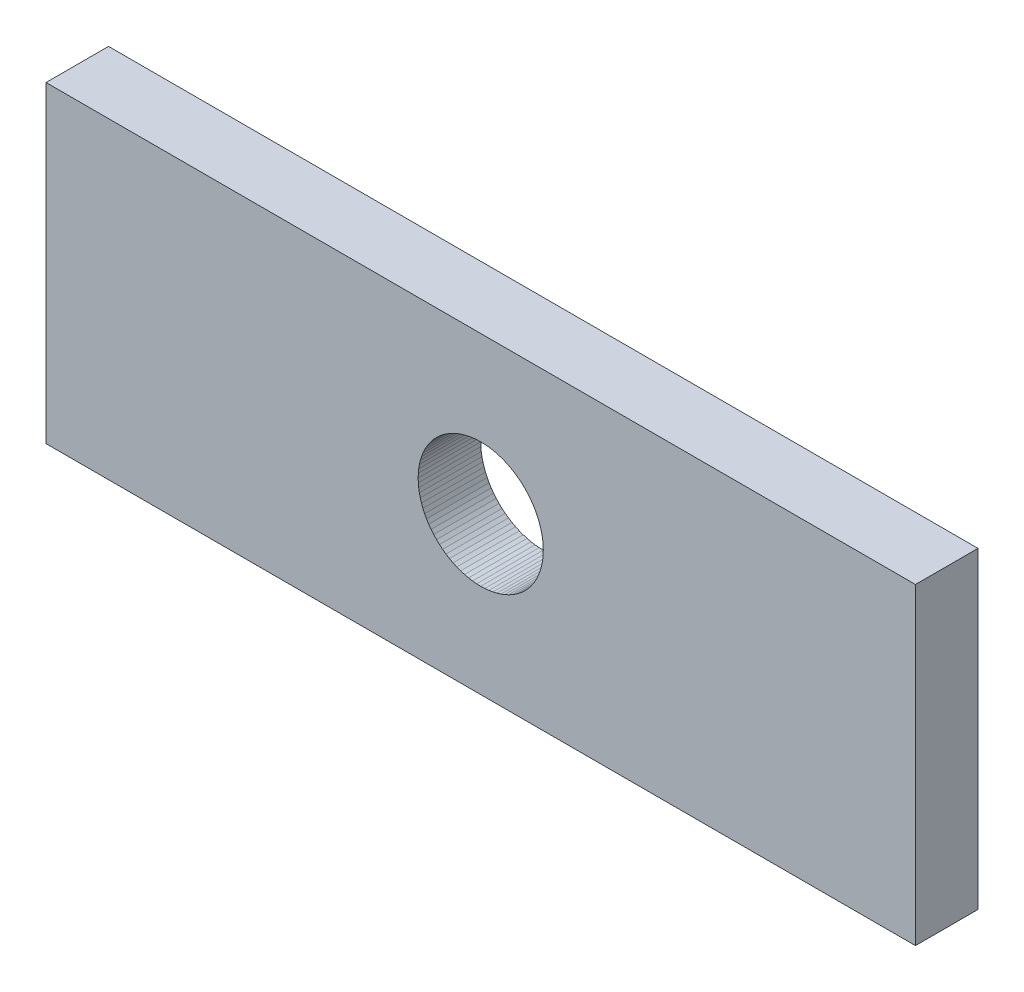
SolidWorks part; units mm, degrees
material "Plain Carbon Steel"
ref_plane "Front Plane" through (0, 0, 0) normal (0, 0, 1) x (1, 0, 0)
ref_plane "Top Plane" through (0, 0, 0) normal (0, 1, 0) x (1, 0, 0)
ref_plane "Right Plane" through (0, 0, 0) normal (1, 0, 0) x (0, 0, -1)
sketch "Model" plane through (0, 0, 0) normal (0, 0, 1) x (1, 0, 0)
  line L0 (1403.0457, -188.9412) -> (1403.0457, -213.9412)
  line L1 (1373.1253, -200.1471) -> (1373.0303, -199.834)
  line L2 (1373.2957, -201.4412) -> (1373.285, -201.1142)
  line L3 (1373.285, -201.7682) -> (1373.2957, -201.4412)
  line L4 (1372.2624, -204.485) -> (1372.453, -204.219)
  line L5 (1372.9151, -199.5278) -> (1372.78, -199.2297)
  line L6 (1371.0735, -205.5985) -> (1371.3395, -205.4079)
  line L7 (1372.9151, -203.3546) -> (1373.0303, -203.0484)
  line L8 (1372.78, -203.6526) -> (1372.9151, -203.3546)
  line L9 (1373.0303, -199.834) -> (1372.9151, -199.5278)
  line L10 (1372.6258, -203.9412) -> (1372.78, -203.6526)
  line L11 (1370.5071, -205.9255) -> (1370.7957, -205.7713)
  line L12 (1372.453, -204.219) -> (1372.6258, -203.9412)
  line L13 (1370.2091, -206.0606) -> (1370.5071, -205.9255)
  line L14 (1373.2529, -200.7885) -> (1373.1996, -200.4657)
  line L15 (1369.5898, -206.2708) -> (1369.9029, -206.1758)
  line L16 (1371.5924, -205.2004) -> (1371.8312, -204.9767)
  line L17 (1370.7957, -205.7713) -> (1371.0735, -205.5985)
  line L18 (1369.2711, -206.3451) -> (1369.5898, -206.2708)
  line L19 (1372.0549, -204.7379) -> (1372.2624, -204.485)
  line L20 (1373.285, -201.1142) -> (1373.2529, -200.7885)
  line L21 (1373.1996, -200.4657) -> (1373.1253, -200.1471)
  line L22 (1363.3064, -201.1142) -> (1363.2957, -201.4412)
  line L23 (1365.7957, -205.7713) -> (1366.0842, -205.9255)
  line L24 (1367.3202, -206.3451) -> (1367.643, -206.3984)
  line L25 (1363.3064, -201.7682) -> (1363.3384, -202.0938)
  line L26 (1333.5457, -188.9412) -> (1403.0457, -188.9412)
  line L27 (1333.5457, -213.9412) -> (1333.5457, -188.9412)
  line L28 (1403.0457, -213.9412) -> (1333.5457, -213.9412)
  line L29 (1373.2529, -202.0938) -> (1373.285, -201.7682)
  line L30 (1373.1996, -202.4166) -> (1373.2529, -202.0938)
  line L31 (1373.1253, -202.7353) -> (1373.1996, -202.4166)
  line L32 (1373.0303, -203.0484) -> (1373.1253, -202.7353)
  line L33 (1371.8312, -204.9767) -> (1372.0549, -204.7379)
  line L34 (1371.3395, -205.4079) -> (1371.5924, -205.2004)
  line L35 (1369.9029, -206.1758) -> (1370.2091, -206.0606)
  line L36 (1368.9483, -206.3984) -> (1369.2711, -206.3451)
  line L37 (1368.6227, -206.4305) -> (1368.9483, -206.3984)
  line L38 (1368.2957, -206.4412) -> (1368.6227, -206.4305)
  line L39 (1367.9686, -206.4305) -> (1368.2957, -206.4412)
  line L40 (1367.643, -206.3984) -> (1367.9686, -206.4305)
  line L41 (1367.0016, -206.2708) -> (1367.3202, -206.3451)
  line L42 (1366.6885, -206.1758) -> (1367.0016, -206.2708)
  line L43 (1366.3822, -206.0606) -> (1366.6885, -206.1758)
  line L44 (1366.0842, -205.9255) -> (1366.3822, -206.0606)
  line L45 (1365.5178, -205.5985) -> (1365.7957, -205.7713)
  line L46 (1365.2519, -205.4079) -> (1365.5178, -205.5985)
  line L47 (1364.9989, -205.2004) -> (1365.2519, -205.4079)
  line L48 (1364.7601, -204.9767) -> (1364.9989, -205.2004)
  line L49 (1364.5365, -204.7379) -> (1364.7601, -204.9767)
  line L50 (1364.3289, -204.485) -> (1364.5365, -204.7379)
  line L51 (1364.1383, -204.219) -> (1364.3289, -204.485)
  line L52 (1363.9655, -203.9412) -> (1364.1383, -204.219)
  line L53 (1363.8113, -203.6526) -> (1363.9655, -203.9412)
  line L54 (1363.6763, -203.3546) -> (1363.8113, -203.6526)
  line L55 (1363.561, -203.0484) -> (1363.6763, -203.3546)
  line L56 (1363.466, -202.7353) -> (1363.561, -203.0484)
  line L57 (1363.3917, -202.4166) -> (1363.466, -202.7353)
  line L58 (1363.3384, -202.0938) -> (1363.3917, -202.4166)
  line L59 (1363.2957, -201.4412) -> (1363.3064, -201.7682)
  line L60 (1363.3384, -200.7885) -> (1363.3064, -201.1142)
  line L61 (1363.3917, -200.4657) -> (1363.3384, -200.7885)
  line L62 (1363.466, -200.1471) -> (1363.3917, -200.4657)
  line L63 (1363.561, -199.834) -> (1363.466, -200.1471)
  line L64 (1363.6763, -199.5278) -> (1363.561, -199.834)
  line L65 (1363.8113, -199.2297) -> (1363.6763, -199.5278)
  line L66 (1363.9655, -198.9412) -> (1363.8113, -199.2297)
  line L67 (1364.1383, -198.6633) -> (1363.9655, -198.9412)
  line L68 (1364.3289, -198.3974) -> (1364.1383, -198.6633)
  line L69 (1364.5365, -198.1444) -> (1364.3289, -198.3974)
  line L70 (1364.7601, -197.9056) -> (1364.5365, -198.1444)
  line L71 (1364.9989, -197.682) -> (1364.7601, -197.9056)
  line L72 (1365.2519, -197.4744) -> (1364.9989, -197.682)
  line L73 (1365.5178, -197.2838) -> (1365.2519, -197.4744)
  line L74 (1365.7957, -197.111) -> (1365.5178, -197.2838)
  line L75 (1366.0842, -196.9568) -> (1365.7957, -197.111)
  line L76 (1366.3822, -196.8218) -> (1366.0842, -196.9568)
  line L77 (1366.6885, -196.7065) -> (1366.3822, -196.8218)
  line L78 (1367.0016, -196.6115) -> (1366.6885, -196.7065)
  line L79 (1367.3202, -196.5372) -> (1367.0016, -196.6115)
  line L80 (1367.643, -196.4839) -> (1367.3202, -196.5372)
  line L81 (1367.9686, -196.4519) -> (1367.643, -196.4839)
  line L82 (1368.2957, -196.4412) -> (1367.9686, -196.4519)
  line L83 (1368.6227, -196.4519) -> (1368.2957, -196.4412)
  line L84 (1368.9483, -196.4839) -> (1368.6227, -196.4519)
  line L85 (1369.2711, -196.5372) -> (1368.9483, -196.4839)
  line L86 (1369.5898, -196.6115) -> (1369.2711, -196.5372)
  line L87 (1369.9029, -196.7065) -> (1369.5898, -196.6115)
  line L88 (1370.2091, -196.8218) -> (1369.9029, -196.7065)
  line L89 (1370.5071, -196.9568) -> (1370.2091, -196.8218)
  line L90 (1370.7957, -197.111) -> (1370.5071, -196.9568)
  line L91 (1371.0735, -197.2838) -> (1370.7957, -197.111)
  line L92 (1371.3395, -197.4744) -> (1371.0735, -197.2838)
  line L93 (1371.5924, -197.682) -> (1371.3395, -197.4744)
  line L94 (1371.8312, -197.9056) -> (1371.5924, -197.682)
  line L95 (1372.0549, -198.1444) -> (1371.8312, -197.9056)
  line L96 (1372.2624, -198.3974) -> (1372.0549, -198.1444)
  line L97 (1372.453, -198.6633) -> (1372.2624, -198.3974)
  line L98 (1372.6258, -198.9412) -> (1372.453, -198.6633)
  line L99 (1372.78, -199.2297) -> (1372.6258, -198.9412)
  line L100 (1377.5683, -197.1332) -> (1379.6039, -197.1332)
  line L101 (1379.6039, -197.1332) -> (1380.4718, -197.205)
  line L102 (1380.4718, -197.205) -> (1381.2023, -197.4204)
  line L103 (1381.2023, -197.4204) -> (1381.6893, -197.7326)
  line L104 (1381.6893, -197.7326) -> (1381.8111, -197.9074)
  line L105 (1381.8111, -197.9074) -> (1381.8517, -198.0947)
  line L106 (1381.8517, -204.7876) -> (1381.8111, -204.9804)
  line L107 (1381.8111, -204.9804) -> (1381.6893, -205.1591)
  line L108 (1381.6893, -205.1591) -> (1381.2023, -205.4744)
  line L109 (1381.2023, -205.4744) -> (1380.4905, -205.6804)
  line L110 (1380.4905, -205.6804) -> (1379.6039, -205.7491)
  line L111 (1379.6039, -205.7491) -> (1377.5683, -205.7491)
  line L112 (1377.5683, -205.7491) -> (1379.6039, -205.7491)
  line L113 (1379.6039, -205.7491) -> (1380.4905, -205.6804)
  line L114 (1380.4905, -205.6804) -> (1381.2023, -205.4744)
  line L115 (1381.2023, -205.4744) -> (1381.6893, -205.1591)
  line L116 (1381.6893, -205.1591) -> (1381.8111, -204.9804)
  line L117 (1381.8111, -204.9804) -> (1381.8517, -204.7876)
  line L118 (1381.8517, -204.7876) -> (1381.8517, -201.4412)
  line L119 (1381.8517, -198.0947) -> (1381.8111, -197.9074)
  line L120 (1381.8111, -197.9074) -> (1381.6893, -197.7326)
  line L121 (1381.6893, -197.7326) -> (1381.2023, -197.4204)
  line L122 (1381.2023, -197.4204) -> (1380.4718, -197.205)
  line L123 (1380.4718, -197.205) -> (1379.6039, -197.1332)
  line L124 (1379.6039, -197.1332) -> (1377.5683, -197.1332)
  line L125 (1387.9329, -205.7491) -> (1386.8106, -201.4412)
  line L126 (1385.6851, -197.121) -> (1384.6222, -201.4412)
  line L127 (1391.6291, -197.121) -> (1389.5561, -198.5569)
  line L128 (1389.5561, -198.5569) -> (1391.6291, -197.121)
  line L129 (1391.6291, -197.121) -> (1391.6291, -205.7491)
  line L130 (1391.6291, -205.7491) -> (1391.6291, -197.121)
  line L131 (1393.55, -205.0998) -> (1393.5902, -205.2824)
  line L132 (1393.5902, -205.2824) -> (1393.7108, -205.4307)
  line L133 (1393.7108, -205.4307) -> (1394.1931, -205.6242)
  line L134 (1394.1931, -205.6242) -> (1395.7979, -205.7491)
  line L135 (1395.7979, -205.7491) -> (1397.4026, -205.6242)
  line L136 (1397.4026, -205.6242) -> (1397.8849, -205.4307)
  line L137 (1397.8849, -205.4307) -> (1398.0055, -205.2824)
  line L138 (1398.0055, -205.2824) -> (1398.0457, -205.0998)
  line L139 (1398.0457, -205.0998) -> (1398.0457, -197.795)
  line L140 (1398.0457, -197.795) -> (1398.0055, -197.612)
  line L141 (1398.0055, -197.612) -> (1397.8849, -197.4626)
  line L142 (1397.8849, -197.4626) -> (1397.4026, -197.2643)
  line L143 (1397.4026, -197.2643) -> (1396.6798, -197.166)
  line L144 (1396.6798, -197.166) -> (1395.7979, -197.1332)
  line L145 (1395.7979, -197.1332) -> (1394.9159, -197.166)
  line L146 (1394.9159, -197.166) -> (1394.1931, -197.2643)
  line L147 (1394.1931, -197.2643) -> (1393.7108, -197.4626)
  line L148 (1393.7108, -197.4626) -> (1393.5902, -197.612)
  line L149 (1393.5902, -197.612) -> (1393.55, -197.795)
  line L150 (1393.55, -197.795) -> (1393.55, -205.0998)
  line L151 (1398.0457, -205.0998) -> (1398.0055, -205.2824)
  line L152 (1398.0055, -205.2824) -> (1397.8849, -205.4307)
  line L153 (1397.8849, -205.4307) -> (1397.4026, -205.6242)
  line L154 (1397.4026, -205.6242) -> (1395.7979, -205.7491)
  line L155 (1395.7979, -205.7491) -> (1394.1931, -205.6242)
  line L156 (1394.1931, -205.6242) -> (1393.7108, -205.4307)
  line L157 (1393.7108, -205.4307) -> (1393.5902, -205.2824)
  line L158 (1393.5902, -205.2824) -> (1393.55, -205.0998)
  line L159 (1393.55, -205.0998) -> (1393.55, -197.795)
  line L160 (1393.55, -197.795) -> (1393.5902, -197.612)
  line L161 (1393.5902, -197.612) -> (1393.7108, -197.4626)
  line L162 (1393.7108, -197.4626) -> (1394.1931, -197.2643)
  line L163 (1394.1931, -197.2643) -> (1394.9159, -197.166)
  line L164 (1394.9159, -197.166) -> (1395.7979, -197.1332)
  line L165 (1395.7979, -197.1332) -> (1396.6798, -197.166)
  line L166 (1396.6798, -197.166) -> (1397.4026, -197.2643)
  line L167 (1397.4026, -197.2643) -> (1397.8849, -197.4626)
  line L168 (1397.8849, -197.4626) -> (1398.0055, -197.612)
  line L169 (1398.0055, -197.612) -> (1398.0457, -197.795)
  line L170 (1398.0457, -197.795) -> (1398.0457, -205.0998)
  line L171 (1377.5683, -205.7491) -> (1377.5683, -197.1332)
  line L172 (1381.8517, -201.4412) -> (1381.8517, -198.0947)
  line L173 (1386.8106, -201.4412) -> (1385.6851, -197.121)
  line L174 (1384.6222, -201.4412) -> (1383.5622, -205.7491)
  line L175 (1384.6222, -201.4412) -> (1386.8106, -201.4412)
  line L176 (1377.5683, -206.7491) -> (1398.0457, -206.7491)
  point P145 (0, 0)
sketch "Sketch1" plane through (0, 0, 0) normal (0, 0, 1) x (1, 0, 0)
  line L0 (1333.5457, -213.9412) -> (1333.5457, -188.9412) construction
  line L1 (1403.0457, -213.9412) -> (1333.5457, -213.9412) construction
  line L2 (1403.0457, -188.9412) -> (1403.0457, -213.9412) construction
  line L3 (1333.5457, -188.9412) -> (1403.0457, -188.9412) construction
  line L4 (1333.5457, -213.9412) -> (1333.5457, -188.9412)
  line L5 (1403.0457, -213.9412) -> (1333.5457, -213.9412)
  line L6 (1403.0457, -188.9412) -> (1403.0457, -213.9412)
  line L7 (1333.5457, -188.9412) -> (1403.0457, -188.9412)
  line L8 (1370.7957, -197.111) -> (1370.5071, -196.9568) construction
  line L9 (1371.0735, -197.2838) -> (1370.7957, -197.111) construction
  line L10 (1371.3395, -197.4744) -> (1371.0735, -197.2838) construction
  line L11 (1371.5924, -197.682) -> (1371.3395, -197.4744) construction
  line L12 (1371.8312, -197.9056) -> (1371.5924, -197.682) construction
  line L13 (1372.0549, -198.1444) -> (1371.8312, -197.9056) construction
  line L14 (1372.2624, -198.3974) -> (1372.0549, -198.1444) construction
  line L15 (1372.453, -198.6633) -> (1372.2624, -198.3974) construction
  line L16 (1372.6258, -198.9412) -> (1372.453, -198.6633) construction
  line L17 (1372.78, -199.2297) -> (1372.6258, -198.9412) construction
  line L18 (1372.9151, -199.5278) -> (1372.78, -199.2297) construction
  line L19 (1373.0303, -199.834) -> (1372.9151, -199.5278) construction
  line L20 (1373.1253, -200.1471) -> (1373.0303, -199.834) construction
  line L21 (1373.1996, -200.4657) -> (1373.1253, -200.1471) construction
  line L22 (1373.2529, -200.7885) -> (1373.1996, -200.4657) construction
  line L23 (1373.285, -201.1142) -> (1373.2529, -200.7885) construction
  line L24 (1373.2957, -201.4412) -> (1373.285, -201.1142) construction
  line L25 (1373.285, -201.7682) -> (1373.2957, -201.4412) construction
  line L26 (1373.2529, -202.0938) -> (1373.285, -201.7682) construction
  line L27 (1373.1996, -202.4166) -> (1373.2529, -202.0938) construction
  line L28 (1373.1253, -202.7353) -> (1373.1996, -202.4166) construction
  line L29 (1373.0303, -203.0484) -> (1373.1253, -202.7353) construction
  line L30 (1372.9151, -203.3546) -> (1373.0303, -203.0484) construction
  line L31 (1372.78, -203.6526) -> (1372.9151, -203.3546) construction
  line L32 (1372.6258, -203.9412) -> (1372.78, -203.6526) construction
  line L33 (1372.453, -204.219) -> (1372.6258, -203.9412) construction
  line L34 (1372.2624, -204.485) -> (1372.453, -204.219) construction
  line L35 (1372.0549, -204.7379) -> (1372.2624, -204.485) construction
  line L36 (1371.8312, -204.9767) -> (1372.0549, -204.7379) construction
  line L37 (1371.5924, -205.2004) -> (1371.8312, -204.9767) construction
  line L38 (1371.3395, -205.4079) -> (1371.5924, -205.2004) construction
  line L39 (1371.0735, -205.5985) -> (1371.3395, -205.4079) construction
  line L40 (1370.7957, -205.7713) -> (1371.0735, -205.5985) construction
  line L41 (1370.5071, -205.9255) -> (1370.7957, -205.7713) construction
  line L42 (1370.2091, -206.0606) -> (1370.5071, -205.9255) construction
  line L43 (1369.9029, -206.1758) -> (1370.2091, -206.0606) construction
  line L44 (1369.5898, -206.2708) -> (1369.9029, -206.1758) construction
  line L45 (1369.2711, -206.3451) -> (1369.5898, -206.2708) construction
  line L46 (1368.9483, -206.3984) -> (1369.2711, -206.3451) construction
  line L47 (1368.6227, -206.4305) -> (1368.9483, -206.3984) construction
  line L48 (1368.2957, -206.4412) -> (1368.6227, -206.4305) construction
  line L49 (1367.9686, -206.4305) -> (1368.2957, -206.4412) construction
  line L50 (1367.643, -206.3984) -> (1367.9686, -206.4305) construction
  line L51 (1367.3202, -206.3451) -> (1367.643, -206.3984) construction
  line L52 (1367.0016, -206.2708) -> (1367.3202, -206.3451) construction
  line L53 (1366.6885, -206.1758) -> (1367.0016, -206.2708) construction
  line L54 (1366.3822, -206.0606) -> (1366.6885, -206.1758) construction
  line L55 (1366.0842, -205.9255) -> (1366.3822, -206.0606) construction
  line L56 (1365.7957, -205.7713) -> (1366.0842, -205.9255) construction
  line L57 (1365.5178, -205.5985) -> (1365.7957, -205.7713) construction
  line L58 (1365.2519, -205.4079) -> (1365.5178, -205.5985) construction
  line L59 (1364.9989, -205.2004) -> (1365.2519, -205.4079) construction
  line L60 (1364.7601, -204.9767) -> (1364.9989, -205.2004) construction
  line L61 (1364.5365, -204.7379) -> (1364.7601, -204.9767) construction
  line L62 (1364.3289, -204.485) -> (1364.5365, -204.7379) construction
  line L63 (1364.1383, -204.219) -> (1364.3289, -204.485) construction
  line L64 (1363.9655, -203.9412) -> (1364.1383, -204.219) construction
  line L65 (1363.8113, -203.6526) -> (1363.9655, -203.9412) construction
  line L66 (1363.6763, -203.3546) -> (1363.8113, -203.6526) construction
  line L67 (1363.561, -203.0484) -> (1363.6763, -203.3546) construction
  line L68 (1363.466, -202.7353) -> (1363.561, -203.0484) construction
  line L69 (1363.3917, -202.4166) -> (1363.466, -202.7353) construction
  line L70 (1363.3384, -202.0938) -> (1363.3917, -202.4166) construction
  line L71 (1363.3064, -201.7682) -> (1363.3384, -202.0938) construction
  line L72 (1363.2957, -201.4412) -> (1363.3064, -201.7682) construction
  line L73 (1363.3064, -201.1142) -> (1363.2957, -201.4412) construction
  line L74 (1363.3384, -200.7885) -> (1363.3064, -201.1142) construction
  line L75 (1363.3917, -200.4657) -> (1363.3384, -200.7885) construction
  line L76 (1363.466, -200.1471) -> (1363.3917, -200.4657) construction
  line L77 (1363.561, -199.834) -> (1363.466, -200.1471) construction
  line L78 (1363.6763, -199.5278) -> (1363.561, -199.834) construction
  line L79 (1363.8113, -199.2297) -> (1363.6763, -199.5278) construction
  line L80 (1363.9655, -198.9412) -> (1363.8113, -199.2297) construction
  line L81 (1364.1383, -198.6633) -> (1363.9655, -198.9412) construction
  line L82 (1364.3289, -198.3974) -> (1364.1383, -198.6633) construction
  line L83 (1364.5365, -198.1444) -> (1364.3289, -198.3974) construction
  line L84 (1364.7601, -197.9056) -> (1364.5365, -198.1444) construction
  line L85 (1364.9989, -197.682) -> (1364.7601, -197.9056) construction
  line L86 (1365.2519, -197.4744) -> (1364.9989, -197.682) construction
  line L87 (1365.5178, -197.2838) -> (1365.2519, -197.4744) construction
  line L88 (1365.7957, -197.111) -> (1365.5178, -197.2838) construction
  line L89 (1366.0842, -196.9568) -> (1365.7957, -197.111) construction
  line L90 (1366.3822, -196.8218) -> (1366.0842, -196.9568) construction
  line L91 (1366.6885, -196.7065) -> (1366.3822, -196.8218) construction
  line L92 (1367.0016, -196.6115) -> (1366.6885, -196.7065) construction
  line L93 (1367.3202, -196.5372) -> (1367.0016, -196.6115) construction
  line L94 (1367.643, -196.4839) -> (1367.3202, -196.5372) construction
  line L95 (1367.9686, -196.4519) -> (1367.643, -196.4839) construction
  line L96 (1368.2957, -196.4412) -> (1367.9686, -196.4519) construction
  line L97 (1368.6227, -196.4519) -> (1368.2957, -196.4412) construction
  line L98 (1368.9483, -196.4839) -> (1368.6227, -196.4519) construction
  line L99 (1369.2711, -196.5372) -> (1368.9483, -196.4839) construction
  line L100 (1369.5898, -196.6115) -> (1369.2711, -196.5372) construction
  line L101 (1369.9029, -196.7065) -> (1369.5898, -196.6115) construction
  line L102 (1370.2091, -196.8218) -> (1369.9029, -196.7065) construction
  line L103 (1370.5071, -196.9568) -> (1370.2091, -196.8218) construction
  line L104 (1370.7957, -197.111) -> (1370.5071, -196.9568)
  line L105 (1371.0735, -197.2838) -> (1370.7957, -197.111)
  line L106 (1371.3395, -197.4744) -> (1371.0735, -197.2838)
  line L107 (1371.5924, -197.682) -> (1371.3395, -197.4744)
  line L108 (1371.8312, -197.9056) -> (1371.5924, -197.682)
  line L109 (1372.0549, -198.1444) -> (1371.8312, -197.9056)
  line L110 (1372.2624, -198.3974) -> (1372.0549, -198.1444)
  line L111 (1372.453, -198.6633) -> (1372.2624, -198.3974)
  line L112 (1372.6258, -198.9412) -> (1372.453, -198.6633)
  line L113 (1372.78, -199.2297) -> (1372.6258, -198.9412)
  line L114 (1372.9151, -199.5278) -> (1372.78, -199.2297)
  line L115 (1373.0303, -199.834) -> (1372.9151, -199.5278)
  line L116 (1373.1253, -200.1471) -> (1373.0303, -199.834)
  line L117 (1373.1996, -200.4657) -> (1373.1253, -200.1471)
  line L118 (1373.2529, -200.7885) -> (1373.1996, -200.4657)
  line L119 (1373.285, -201.1142) -> (1373.2529, -200.7885)
  line L120 (1373.2957, -201.4412) -> (1373.285, -201.1142)
  line L121 (1373.285, -201.7682) -> (1373.2957, -201.4412)
  line L122 (1373.2529, -202.0938) -> (1373.285, -201.7682)
  line L123 (1373.1996, -202.4166) -> (1373.2529, -202.0938)
  line L124 (1373.1253, -202.7353) -> (1373.1996, -202.4166)
  line L125 (1373.0303, -203.0484) -> (1373.1253, -202.7353)
  line L126 (1372.9151, -203.3546) -> (1373.0303, -203.0484)
  line L127 (1372.78, -203.6526) -> (1372.9151, -203.3546)
  line L128 (1372.6258, -203.9412) -> (1372.78, -203.6526)
  line L129 (1372.453, -204.219) -> (1372.6258, -203.9412)
  line L130 (1372.2624, -204.485) -> (1372.453, -204.219)
  line L131 (1372.0549, -204.7379) -> (1372.2624, -204.485)
  line L132 (1371.8312, -204.9767) -> (1372.0549, -204.7379)
  line L133 (1371.5924, -205.2004) -> (1371.8312, -204.9767)
  line L134 (1371.3395, -205.4079) -> (1371.5924, -205.2004)
  line L135 (1371.0735, -205.5985) -> (1371.3395, -205.4079)
  line L136 (1370.7957, -205.7713) -> (1371.0735, -205.5985)
  line L137 (1370.5071, -205.9255) -> (1370.7957, -205.7713)
  line L138 (1370.2091, -206.0606) -> (1370.5071, -205.9255)
  line L139 (1369.9029, -206.1758) -> (1370.2091, -206.0606)
  line L140 (1369.5898, -206.2708) -> (1369.9029, -206.1758)
  line L141 (1369.2711, -206.3451) -> (1369.5898, -206.2708)
  line L142 (1368.9483, -206.3984) -> (1369.2711, -206.3451)
  line L143 (1368.6227, -206.4305) -> (1368.9483, -206.3984)
  line L144 (1368.2957, -206.4412) -> (1368.6227, -206.4305)
  line L145 (1367.9686, -206.4305) -> (1368.2957, -206.4412)
  line L146 (1367.643, -206.3984) -> (1367.9686, -206.4305)
  line L147 (1367.3202, -206.3451) -> (1367.643, -206.3984)
  line L148 (1367.0016, -206.2708) -> (1367.3202, -206.3451)
  line L149 (1366.6885, -206.1758) -> (1367.0016, -206.2708)
  line L150 (1366.3822, -206.0606) -> (1366.6885, -206.1758)
  line L151 (1366.0842, -205.9255) -> (1366.3822, -206.0606)
  line L152 (1365.7957, -205.7713) -> (1366.0842, -205.9255)
  line L153 (1365.5178, -205.5985) -> (1365.7957, -205.7713)
  line L154 (1365.2519, -205.4079) -> (1365.5178, -205.5985)
  line L155 (1364.9989, -205.2004) -> (1365.2519, -205.4079)
  line L156 (1364.7601, -204.9767) -> (1364.9989, -205.2004)
  line L157 (1364.5365, -204.7379) -> (1364.7601, -204.9767)
  line L158 (1364.3289, -204.485) -> (1364.5365, -204.7379)
  line L159 (1364.1383, -204.219) -> (1364.3289, -204.485)
  line L160 (1363.9655, -203.9412) -> (1364.1383, -204.219)
  line L161 (1363.8113, -203.6526) -> (1363.9655, -203.9412)
  line L162 (1363.6763, -203.3546) -> (1363.8113, -203.6526)
  line L163 (1363.561, -203.0484) -> (1363.6763, -203.3546)
  line L164 (1363.466, -202.7353) -> (1363.561, -203.0484)
  line L165 (1363.3917, -202.4166) -> (1363.466, -202.7353)
  line L166 (1363.3384, -202.0938) -> (1363.3917, -202.4166)
  line L167 (1363.3064, -201.7682) -> (1363.3384, -202.0938)
  line L168 (1363.2957, -201.4412) -> (1363.3064, -201.7682)
  line L169 (1363.3064, -201.1142) -> (1363.2957, -201.4412)
  line L170 (1363.3384, -200.7885) -> (1363.3064, -201.1142)
  line L171 (1363.3917, -200.4657) -> (1363.3384, -200.7885)
  line L172 (1363.466, -200.1471) -> (1363.3917, -200.4657)
  line L173 (1363.561, -199.834) -> (1363.466, -200.1471)
  line L174 (1363.6763, -199.5278) -> (1363.561, -199.834)
  line L175 (1363.8113, -199.2297) -> (1363.6763, -199.5278)
  line L176 (1363.9655, -198.9412) -> (1363.8113, -199.2297)
  line L177 (1364.1383, -198.6633) -> (1363.9655, -198.9412)
  line L178 (1364.3289, -198.3974) -> (1364.1383, -198.6633)
  line L179 (1364.5365, -198.1444) -> (1364.3289, -198.3974)
  line L180 (1364.7601, -197.9056) -> (1364.5365, -198.1444)
  line L181 (1364.9989, -197.682) -> (1364.7601, -197.9056)
  line L182 (1365.2519, -197.4744) -> (1364.9989, -197.682)
  line L183 (1365.5178, -197.2838) -> (1365.2519, -197.4744)
  line L184 (1365.7957, -197.111) -> (1365.5178, -197.2838)
  line L185 (1366.0842, -196.9568) -> (1365.7957, -197.111)
  line L186 (1366.3822, -196.8218) -> (1366.0842, -196.9568)
  line L187 (1366.6885, -196.7065) -> (1366.3822, -196.8218)
  line L188 (1367.0016, -196.6115) -> (1366.6885, -196.7065)
  line L189 (1367.3202, -196.5372) -> (1367.0016, -196.6115)
  line L190 (1367.643, -196.4839) -> (1367.3202, -196.5372)
  line L191 (1367.9686, -196.4519) -> (1367.643, -196.4839)
  line L192 (1368.2957, -196.4412) -> (1367.9686, -196.4519)
  line L193 (1368.6227, -196.4519) -> (1368.2957, -196.4412)
  line L194 (1368.9483, -196.4839) -> (1368.6227, -196.4519)
  line L195 (1369.2711, -196.5372) -> (1368.9483, -196.4839)
  line L196 (1369.5898, -196.6115) -> (1369.2711, -196.5372)
  line L197 (1369.9029, -196.7065) -> (1369.5898, -196.6115)
  line L198 (1370.2091, -196.8218) -> (1369.9029, -196.7065)
  line L199 (1370.5071, -196.9568) -> (1370.2091, -196.8218)
extrude "Boss-Extrude1" add sketch "Sketch1" along normal mid plane 5
sketch "Sketch2" plane through (0, 0, 2.5) normal (0, 0, 1) x (1, 0, 0)
  circle A0 centre (1368.2957, -201.4412) radius 5
  point P2 (0, 0)
ref_axis "Axis1" through (1368.2957, -201.4412, 2.5) along (0, 0, 1)
